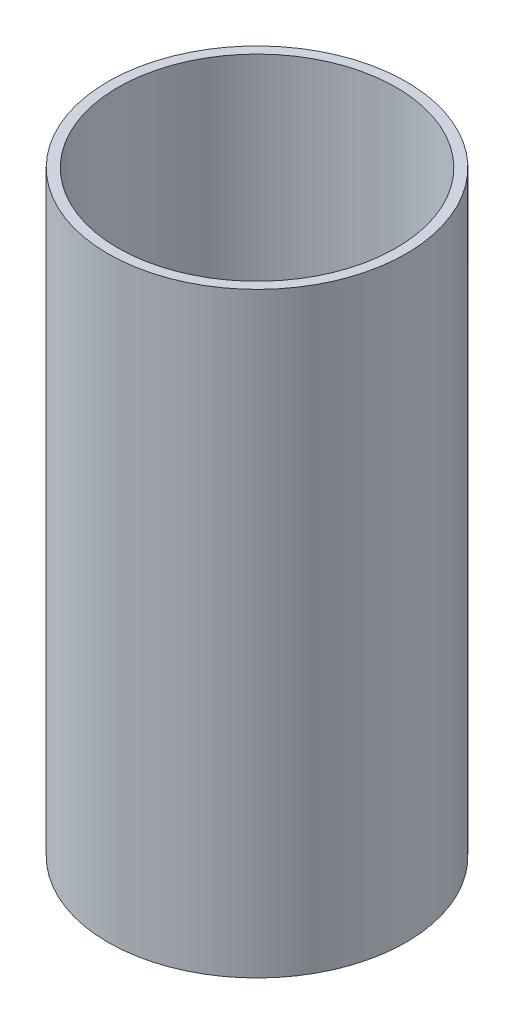
SolidWorks part; units mm, degrees
ref_plane "Plan de face" through (0, 0, 0) normal (0, 0, 1) x (1, 0, 0)
ref_plane "Plan de dessus" through (0, 0, 0) normal (0, 1, 0) x (1, 0, 0)
ref_plane "Plan de droite" through (0, 0, 0) normal (1, 0, 0) x (0, 0, -1)
sketch "Esquisse1" plane through (0, 0, 0) normal (0, 1, 0) x (1, 0, 0)
  circle A0 centre (0, 0) radius 75
  circle A1 centre (0, 0) radius 70
  dimension "D1" = 150
  dimension "D2" = 5
extrude "Boss.-Extru.1" add sketch "Esquisse1" along normal blind 300
ref_plane "Plan1" through (0, 150, 0) normal (0, -1, 0) x (-1, 0, 0)
